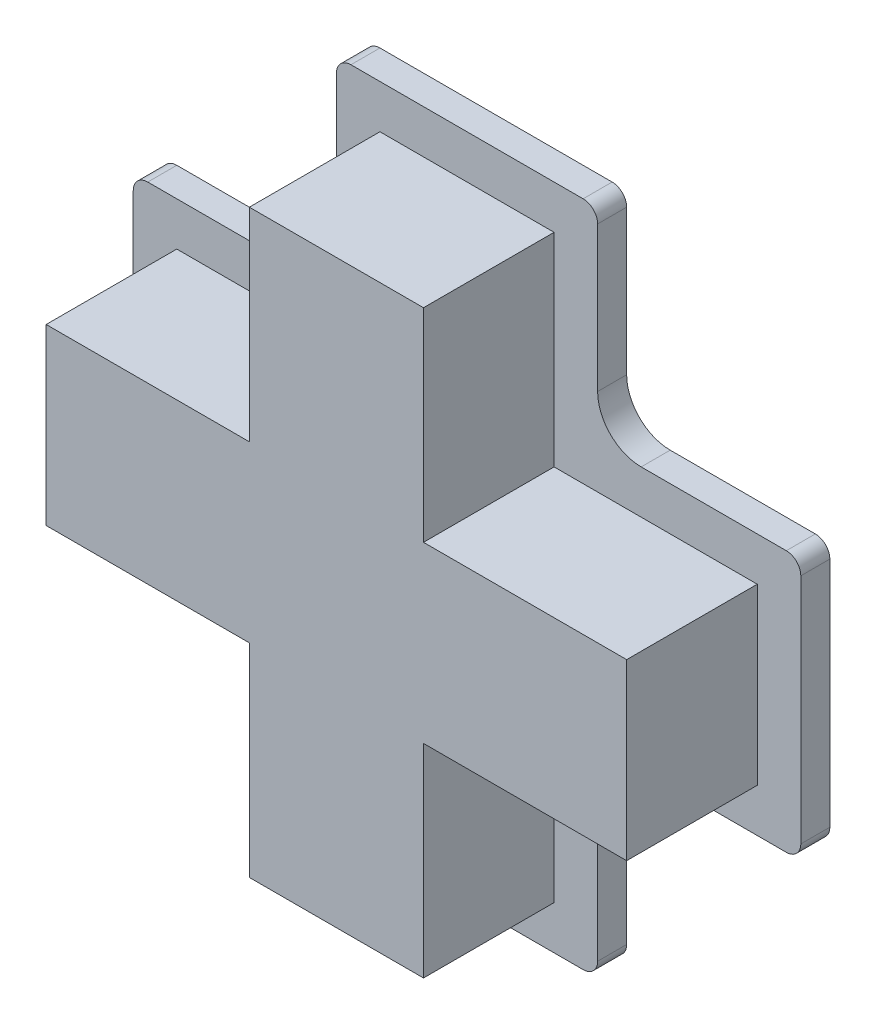
SolidWorks part; units mm, degrees
ref_plane "Front Plane" through (0, 0, 0) normal (0, 0, 1) x (1, 0, 0)
ref_plane "Top Plane" through (0, 0, 0) normal (0, 1, 0) x (1, 0, 0)
ref_plane "Right Plane" through (0, 0, 0) normal (1, 0, 0) x (0, 0, -1)
sketch "Sketch1" plane through (0, 0, 0) normal (0, 0, 1) x (1, 0, 0)
  line L92 (-14.1739, 7.0321) -> (-14.1739, 1.0321)
  line L93 (-14.1739, 1.0321) -> (-7.1739, 1.0321)
  line L94 (-7.1739, 1.0321) -> (-7.1739, -5.9679)
  line L95 (-7.1739, -5.9679) -> (-1.1739, -5.9679)
  line L96 (-1.1739, -5.9679) -> (-1.1739, 1.0321)
  line L97 (-1.1739, 1.0321) -> (5.8261, 1.0321)
  line L98 (5.8261, 1.0321) -> (5.8261, 7.0321)
  line L99 (5.8261, 7.0321) -> (-1.1739, 7.0321)
  line L100 (-1.1739, 7.0321) -> (-1.1739, 14.0321)
  line L101 (-1.1739, 14.0321) -> (-7.1739, 14.0321)
  line L102 (-7.1739, 14.0321) -> (-7.1739, 7.0321)
  line L103 (-7.1739, 7.0321) -> (-14.1739, 7.0321)
  line L104 (-14.1739, 7.0321) -> (-14.1739, 1.0321)
  line L105 (-14.1739, 1.0321) -> (-7.1739, 1.0321)
  line L106 (-7.1739, 1.0321) -> (-7.1739, -5.9679)
  line L107 (-7.1739, -5.9679) -> (-1.1739, -5.9679)
  line L108 (-1.1739, -5.9679) -> (-1.1739, 1.0321)
  line L109 (-1.1739, 1.0321) -> (5.8261, 1.0321)
  line L110 (5.8261, 1.0321) -> (5.8261, 7.0321)
  line L111 (5.8261, 7.0321) -> (-1.1739, 7.0321)
  line L112 (-1.1739, 7.0321) -> (-1.1739, 14.0321)
  line L113 (-1.1739, 14.0321) -> (-7.1739, 14.0321)
  line L114 (-7.1739, 14.0321) -> (-7.1739, 7.0321)
  line L115 (-7.1739, 7.0321) -> (-14.1739, 7.0321)
  dimension "D1" = 0.5
extrude "Boss-Extrude1" add sketch "Sketch1" along normal blind 5.5
sketch "Sketch2" plane through (0, 0, 0) normal (0, 0, 1) x (1, 0, 0)
  line L241 (-15.6739, 8.0321) -> (-15.6739, 0.0321)
  line L242 (-15.1739, -0.4679) -> (-10.1739, -0.4679)
  line L243 (-8.6739, -1.9679) -> (-8.6739, -6.9679)
  line L244 (-8.1739, -7.4679) -> (-0.1739, -7.4679)
  line L245 (0.3261, -6.9679) -> (0.3261, -1.9679)
  line L246 (1.8261, -0.4679) -> (6.8261, -0.4679)
  line L247 (7.3261, 0.0321) -> (7.3261, 8.0321)
  line L248 (6.8261, 8.5321) -> (1.8261, 8.5321)
  line L249 (0.3261, 10.0321) -> (0.3261, 15.0321)
  line L250 (-0.1739, 15.5321) -> (-8.1739, 15.5321)
  line L251 (-8.6739, 15.0321) -> (-8.6739, 10.0321)
  line L252 (-10.1739, 8.5321) -> (-15.1739, 8.5321)
  line L253 (-15.6739, 8.0321) -> (-15.6739, 0.0321)
  line L254 (-15.1739, -0.4679) -> (-10.1739, -0.4679)
  line L255 (-8.6739, -1.9679) -> (-8.6739, -6.9679)
  line L256 (-8.1739, -7.4679) -> (-0.1739, -7.4679)
  line L257 (0.3261, -6.9679) -> (0.3261, -1.9679)
  line L258 (1.8261, -0.4679) -> (6.8261, -0.4679)
  line L259 (7.3261, 0.0321) -> (7.3261, 8.0321)
  line L260 (6.8261, 8.5321) -> (1.8261, 8.5321)
  line L261 (0.3261, 10.0321) -> (0.3261, 15.0321)
  line L262 (-0.1739, 15.5321) -> (-8.1739, 15.5321)
  line L263 (-8.6739, 15.0321) -> (-8.6739, 10.0321)
  line L264 (-10.1739, 8.5321) -> (-15.1739, 8.5321)
  arc A168 (-15.6739, 0.0321) -> (-15.1739, -0.4679) centre (-15.1739, 0.0321) ccw
  arc A169 (-8.6739, -1.9679) -> (-10.1739, -0.4679) centre (-10.1739, -1.9679) ccw
  arc A170 (-8.6739, -6.9679) -> (-8.1739, -7.4679) centre (-8.1739, -6.9679) ccw
  arc A171 (-0.1739, -7.4679) -> (0.3261, -6.9679) centre (-0.1739, -6.9679) ccw
  arc A172 (1.8261, -0.4679) -> (0.3261, -1.9679) centre (1.8261, -1.9679) ccw
  arc A173 (6.8261, -0.4679) -> (7.3261, 0.0321) centre (6.8261, 0.0321) ccw
  arc A174 (7.3261, 8.0321) -> (6.8261, 8.5321) centre (6.8261, 8.0321) ccw
  arc A175 (0.3261, 10.0321) -> (1.8261, 8.5321) centre (1.8261, 10.0321) ccw
  arc A176 (0.3261, 15.0321) -> (-0.1739, 15.5321) centre (-0.1739, 15.0321) ccw
  arc A177 (-8.1739, 15.5321) -> (-8.6739, 15.0321) centre (-8.1739, 15.0321) ccw
  arc A178 (-10.1739, 8.5321) -> (-8.6739, 10.0321) centre (-10.1739, 10.0321) ccw
  arc A179 (-15.1739, 8.5321) -> (-15.6739, 8.0321) centre (-15.1739, 8.0321) ccw
  arc A180 (-15.6739, 0.0321) -> (-15.1739, -0.4679) centre (-15.1739, 0.0321) ccw
  arc A181 (-8.6739, -1.9679) -> (-10.1739, -0.4679) centre (-10.1739, -1.9679) ccw
  arc A182 (-8.6739, -6.9679) -> (-8.1739, -7.4679) centre (-8.1739, -6.9679) ccw
  arc A183 (-0.1739, -7.4679) -> (0.3261, -6.9679) centre (-0.1739, -6.9679) ccw
  arc A184 (1.8261, -0.4679) -> (0.3261, -1.9679) centre (1.8261, -1.9679) ccw
  arc A185 (6.8261, -0.4679) -> (7.3261, 0.0321) centre (6.8261, 0.0321) ccw
  arc A186 (7.3261, 8.0321) -> (6.8261, 8.5321) centre (6.8261, 8.0321) ccw
  arc A187 (0.3261, 10.0321) -> (1.8261, 8.5321) centre (1.8261, 10.0321) ccw
  arc A188 (0.3261, 15.0321) -> (-0.1739, 15.5321) centre (-0.1739, 15.0321) ccw
  arc A189 (-8.1739, 15.5321) -> (-8.6739, 15.0321) centre (-8.1739, 15.0321) ccw
  arc A190 (-10.1739, 8.5321) -> (-8.6739, 10.0321) centre (-10.1739, 10.0321) ccw
  arc A191 (-15.1739, 8.5321) -> (-15.6739, 8.0321) centre (-15.1739, 8.0321) ccw
  dimension "D1" = 0.5
extrude "Boss-Extrude2" add sketch "Sketch2" along normal blind 1
